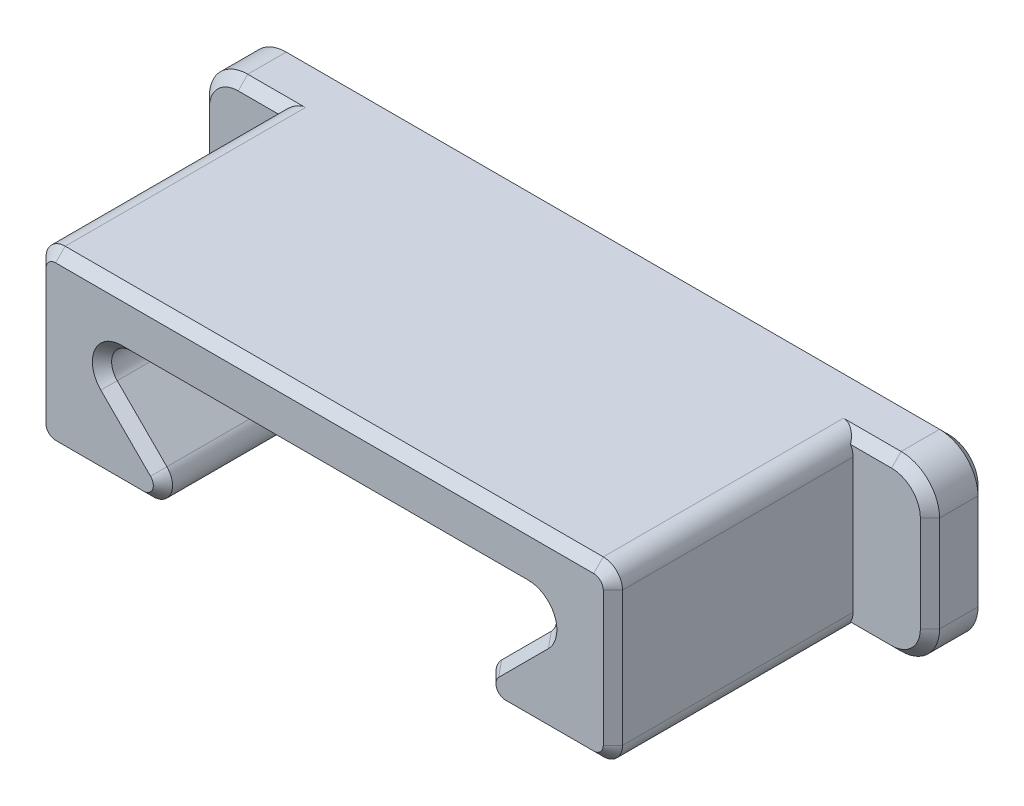
SolidWorks part; units mm, degrees
material "6061 合金"
ref_plane "前视基准面" through (0, 0, 0) normal (0, 0, 1) x (1, 0, 0)
ref_plane "上视基准面" through (0, 0, 0) normal (0, 1, 0) x (1, 0, 0)
ref_plane "右视基准面" through (0, 0, 0) normal (1, 0, 0) x (0, 0, -1)
other "Configuration Table"
sketch "草图1" plane through (0, 0, 0) normal (0, 0, 1) x (1, 0, 0)
  line L0 (-10.0832, 0) -> (8.1555, 0) construction
  line L1 (0, 5.8571) -> (0, -7.8589) construction
  line L3 (-17, -4.5) -> (17, -4.5)
  line L4 (-19, -2.5) -> (-19, 2.5)
  line L5 (-17, 4.5) -> (17, 4.5)
  line L6 (19, -2.5) -> (19, 2.5)
  line L7 (-19, -4.5) -> (19, 4.5) construction
  line L8 (-19, 4.5) -> (19, -4.5) construction
  arc A0 (-19, 2.5) -> (-17, 4.5) centre (-17, 2.5) cw
  arc A1 (-17, -4.5) -> (-19, -2.5) centre (-17, -2.5) cw
  arc A2 (17, -4.5) -> (19, -2.5) centre (17, -2.5) ccw
  arc A3 (17, 4.5) -> (19, 2.5) centre (17, 2.5) cw
  point P4 (0, 0)
  dimension "D3" = 2
  dimension "D1" = 38
  dimension "D2" = 9
extrude "凸台-拉伸1" add sketch "草图1" along normal blind 3
sketch "草图2" plane through (0, 0, 3) normal (0, 0, 1) x (1, 0, 0)
  line L0 (0, 52.105) -> (0, -40.6941) construction
  line L1 (-15, 3.5) -> (-15, -3.5)
  line L2 (-14, -4.5) -> (-9.4142, -4.5)
  line L3 (-8.7071, -2.7929) -> (-11.2929, -0.2071)
  line L4 (-10.5858, 1.5) -> (10.5858, 1.5)
  line L5 (-14, 4.5) -> (14, 4.5)
  line L6 (8.7071, -2.7929) -> (11.2929, -0.2071)
  line L7 (14, -4.5) -> (9.4142, -4.5)
  line L8 (15, 3.5) -> (15, -3.5)
  line L9 (17, 4.5) -> (-17, 4.5) construction
  line L10 (-17, -4.5) -> (17, -4.5) construction
  arc A0 (8.7071, -2.7929) -> (9.4142, -4.5) centre (9.4142, -3.5) ccw
  arc A1 (-9.4142, -4.5) -> (-8.7071, -2.7929) centre (-9.4142, -3.5) ccw
  arc A2 (-15, -3.5) -> (-14, -4.5) centre (-14, -3.5) ccw
  arc A3 (-15, 3.5) -> (-14, 4.5) centre (-14, 3.5) cw
  arc A4 (15, 3.5) -> (14, 4.5) centre (14, 3.5) ccw
  arc A5 (14, -4.5) -> (15, -3.5) centre (14, -3.5) ccw
  arc A6 (-11.2929, -0.2071) -> (-10.5858, 1.5) centre (-10.5858, 0.5) cw
  arc A7 (11.2929, -0.2071) -> (10.5858, 1.5) centre (10.5858, 0.5) ccw
  point P8 (0, 4.5)
  point P9 (0, 1.5)
  point P28 (7.3503, 32.5342)
  point P36 (7, -4.5)
  dimension "D1" = 1
  dimension "D4" = 1
  dimension "D2" = 45
  dimension "D3" = 3
  dimension "D5" = 30
  dimension "D6" = 14
extrude "凸台-拉伸2" add sketch "草图2" along normal blind 12.5
sketch "草图7" plane through (0, 0, 3) normal (0, 0, 1) x (1, 0, 0)
  line L0 (-10.5858, 1.5) -> (10.5858, 1.5) construction
  line L1 (-3.5, 1.5) -> (3.5, 1.5)
  line L2 (-3.5, 1.5) -> (-3.5, -4.5)
  line L3 (-3.5, -4.5) -> (3.5, -4.5)
  line L4 (3.5, 1.5) -> (3.5, -4.5)
  line L5 (-9.4142, -4.5) -> (9.4142, -4.5) construction
  line L6 (0, 6.431) -> (0, -9.2607) construction
  dimension "D1" = 7
extrude "凸台-拉伸3" add sketch "草图7" along normal blind 3
fillet "圆角1" radius 1 4 edges at (-3.5, 1.5, 4.5) (-3.5, -4.5, 4.5) (3.5, -4.5, 4.5) (3.5, 1.5, 4.5)
sketch "草图5" plane through (0, 0, 6) normal (0, 0, 1) x (1, 0, 0)
  line L0 (-9.4142, -4.5) -> (-2.5, -4.5) construction
  point P0 (0, -1.5)
  dimension "D1" = 3
hole_wizard "M3 螺纹孔1" positions "草图5" profile "草图6" tap size "M3" standard "GB" end condition up to next
sketch "草图6" plane through (0, -1.5, 6) normal (1, 0, 0) x (0, -1, 0)
  line L0 (0, 0) -> (0, 6)
  line L1 (0, 6) -> (1.25, 6)
  line L2 (1.25, 6) -> (1.25, 0)
  line L5 (1.25, 0) -> (0, 0)
  line L11 (0, -6.35) -> (0, 107.95) construction
  dimension "通孔螺纹孔钻头直径" = 2.5
  dimension "通孔螺纹孔钻头深度" = 6
cosmetic thread "孔螺蚊线3" parameters "D2"=3
chamfer "倒角1" distance 0.5 angle 45 43 edges at (15.5, -4.5, 3) (18.4142, -3.9142, 3) (19, 0, 3) (18.4142, 3.9142, 3) (15.5, 4.5, 3) (0, 1.5, 15.5) (11.5097, 0.8827, 15.5) (-11.5097, 0.8827, 15.5) (10, -1.5, 15.5) (-10, -1.5, 15.5) (8.4903, -3.8827, 15.5) (-8.4903, -3.8827, 15.5) (11.7071, -4.5, 15.5) (-11.7071, -4.5, 15.5) (14.7071, -4.2071, 15.5) (-14.7071, -4.2071, 15.5) (15, 0, 15.5) (-15, 0, 15.5) (14.7071, 4.2071, 15.5) (-14.7071, 4.2071, 15.5) (0, 4.5, 15.5) (-15.5, -4.5, 3) (-18.4142, -3.9142, 3) (-19, 0, 3) (-18.4142, 3.9142, 3) (-15.5, 4.5, 3) (0, -4.5, 0) (18.4142, -3.9142, 0) (-18.4142, -3.9142, 0) (19, 0, 0) (-19, 0, 0) (18.4142, 3.9142, 0) (-18.4142, 3.9142, 0) (0, 4.5, 0) (-5.9571, -4.5, 3) (5.9571, -4.5, 3) (-3.7929, 1.2071, 6) (-3.5, -1.5, 6) (-3.2071, -4.2071, 6) (3.7929, 1.2071, 6) (0, -4.5, 6) (3.5, -1.5, 6) (3.2071, -4.2071, 6)
